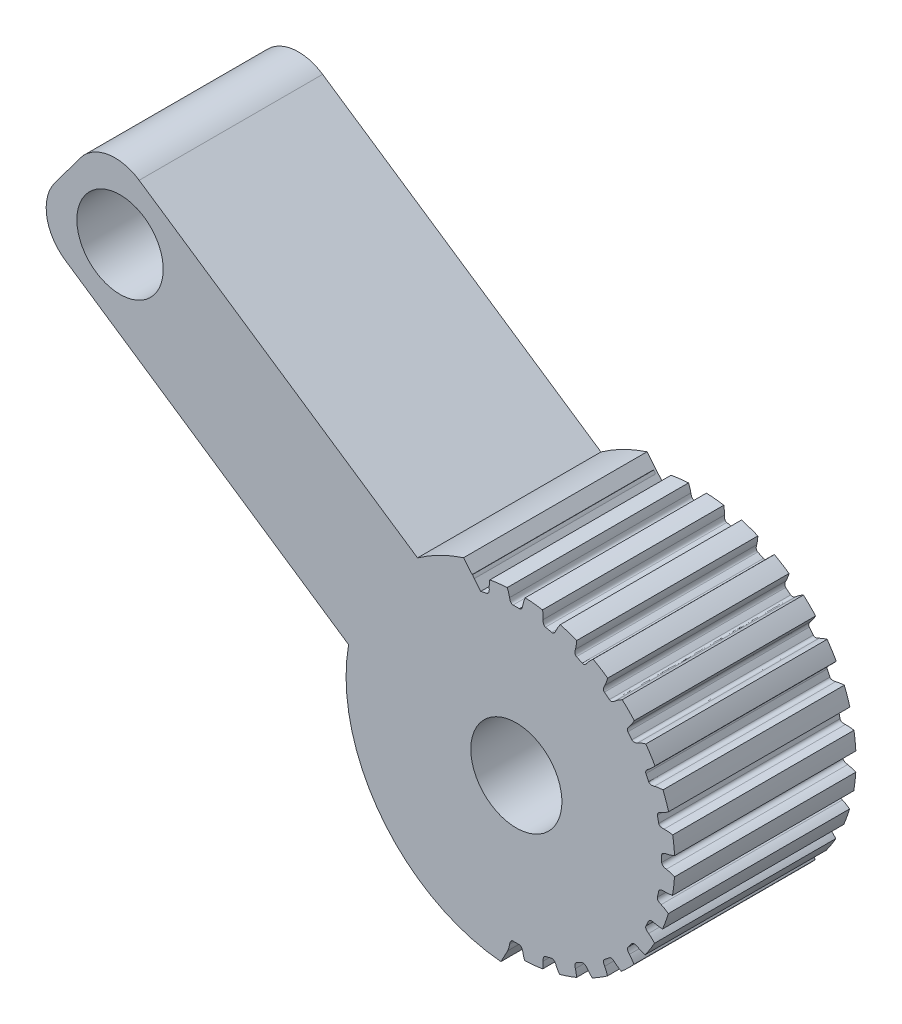
SolidWorks part; units mm, degrees
ref_plane "Front Plane" through (0, 0, 0) normal (0, 0, 1) x (1, 0, 0)
ref_plane "Top Plane" through (0, 0, 0) normal (0, 1, 0) x (1, 0, 0)
ref_plane "Right Plane" through (0, 0, 0) normal (1, 0, 0) x (0, 0, -1)
sketch "Sketch1" plane through (0, 0, 0) normal (0, 0, 1) x (1, 0, 0)
  circle A0 centre (0, 0) radius 51
  spline B0 degree 3 poles (-154.887, 66.78) (-155.2147, 66.8751) (-155.972, 67.0749) (-157.2665, 67.3592) (-158.8688, 67.6411) (-160.7804, 67.8949) (-163.0012, 68.0947) (-165.5296, 68.2148) (-168.3623, 68.2292) (-171.4943, 68.1124) (-174.9189, 67.8391) (-177.2922, 67.5479) (-178.5249, 67.3712) knots 0 0 0 0 0.040302 0.092469 0.156501 0.232397 0.320159 0.419784 0.531275 0.65463 0.789849 0.936934 0.936934 0.936934 0.936934
  spline B1 degree 3 poles (-32.9524, 160.1409) (-32.7131, 160.19) (-32.2573, 160.3561) (-31.6871, 160.7688) (-31.2499, 161.2756) (-30.925, 161.8346) (-30.6851, 162.433) (-30.5112, 163.0721) (-30.3923, 163.7568) (-30.3235, 164.4918) (-30.3029, 165.2808) (-30.3207, 165.8245) (-30.3369, 166.1054) knots 0 0 0 0 0.028845 0.056347 0.082281 0.107325 0.132381 0.15822 0.185411 0.214359 0.245345 0.278571 0.278571 0.278571 0.278571
  spline B2 degree 3 poles (-30.3369, 166.1054) (-30.3567, 166.446) (-30.383, 167.2288) (-30.3721, 168.5541) (-30.2904, 170.179) (-30.1125, 172.0991) (-29.8131, 174.3087) (-29.3675, 176.8004) (-28.7513, 179.5653) (-27.9405, 182.5927) (-26.9119, 185.8707) (-26.1, 188.1197) (-25.6534, 189.2821) knots 0 0 0 0 0.040302 0.092469 0.156501 0.232397 0.320159 0.419784 0.531275 0.65463 0.789849 0.936934 0.936934 0.936934 0.936934
  spline B3 degree 3 poles (-3.6912, 163.4378) (-3.9354, 163.4325) (-4.4167, 163.493) (-5.0645, 163.7685) (-5.6035, 164.1653) (-6.0446, 164.638) (-6.4117, 165.168) (-6.7235, 165.7523) (-6.9917, 166.3934) (-7.2223, 167.0947) (-7.418, 167.8593) (-7.5217, 168.3933) (-7.5683, 168.6708) knots 0 0 0 0 0.028845 0.056347 0.082281 0.107325 0.132381 0.15822 0.185411 0.214359 0.245345 0.278571 0.278571 0.278571 0.278571
  arc B4 (-163.6485, -97.2678) -> (-159.1718, -104.3926) centre (-0.1485, 0.4972) ccw
  spline B5 degree 3 poles (162.1575, 45.1531) (162.473, 45.2831) (163.1896, 45.599) (164.379, 46.1839) (165.8075, 46.9625) (167.4603, 47.9559) (169.3212, 49.1843) (171.3728, 50.6669) (173.5965, 52.4218) (175.9723, 54.4658) (178.4794, 56.8148) (180.1534, 58.5221) (181.0069, 59.4289) knots 0 0 0 0 0.040302 0.092469 0.156501 0.232397 0.320159 0.419784 0.531275 0.65463 0.789849 0.936934 0.936934 0.936934 0.936934
  spline B6 degree 3 poles (-162.4546, 45.1531) (-162.7701, 45.2831) (-163.4867, 45.599) (-164.6761, 46.1839) (-166.1046, 46.9625) (-167.7574, 47.9559) (-169.6183, 49.1843) (-171.6699, 50.6669) (-173.8935, 52.4218) (-176.2694, 54.4658) (-178.7765, 56.8148) (-180.4505, 58.5221) (-181.304, 59.4289) knots 0 0 0 0 0.040302 0.092469 0.156501 0.232397 0.320159 0.419784 0.531275 0.65463 0.789849 0.936934 0.936934 0.936934 0.936934
  spline B7 degree 3 poles (-168.3221, -6.9226) (-168.6586, -6.9791) (-169.4276, -7.1277) (-170.7173, -7.4332) (-172.2832, -7.8744) (-174.1156, -8.4751) (-176.2032, -9.2587) (-178.5333, -10.2476) (-181.0917, -11.4636) (-183.8629, -12.9277) (-186.8298, -14.6599) (-188.8417, -15.9519) (-189.8756, -16.646) knots 0 0 0 0 0.040302 0.092469 0.156501 0.232397 0.320159 0.419784 0.531275 0.65463 0.789849 0.936934 0.936934 0.936934 0.936934
  spline B8 degree 3 poles (-165.7567, -29.6912) (-166.0973, -29.7109) (-166.8801, -29.7372) (-168.2055, -29.7264) (-169.8303, -29.6447) (-171.7504, -29.4667) (-173.96, -29.1674) (-176.4517, -28.7218) (-179.2166, -28.1055) (-182.2441, -27.2947) (-185.5221, -26.2662) (-187.771, -25.4543) (-188.9335, -25.0076) knots 0 0 0 0 0.040302 0.092469 0.156501 0.232397 0.320159 0.419784 0.531275 0.65463 0.789849 0.936934 0.936934 0.936934 0.936934
  arc B9 (3.3942, 163.4378) -> (-3.6912, 163.4378) centre (-0.1485, 0.4972) ccw
  spline B10 degree 3 poles (-7.5683, 168.6708) (-7.6249, 169.0073) (-7.7734, 169.7762) (-8.0789, 171.066) (-8.5201, 172.6319) (-9.1209, 174.4643) (-9.9044, 176.5519) (-10.8933, 178.882) (-12.1093, 181.4404) (-13.5735, 184.2115) (-15.3057, 187.1784) (-16.5977, 189.1903) (-17.2918, 190.2243) knots 0 0 0 0 0.040302 0.092469 0.156501 0.232397 0.320159 0.419784 0.531275 0.65463 0.789849 0.936934 0.936934 0.936934 0.936934
  arc B11 (-17.2918, 190.2243) -> (-25.6534, 189.2821) centre (-0.1485, 0.4972) ccw
  arc B12 (-32.9524, 160.1409) -> (-39.8601, 158.5642) centre (-0.1485, 0.4972) ccw
  spline B13 degree 3 poles (-39.8601, 158.5642) (-40.097, 158.5047) (-40.5797, 158.4566) (-41.2725, 158.581) (-41.8863, 158.8479) (-42.4216, 159.2106) (-42.8973, 159.6457) (-43.3314, 160.1459) (-43.7355, 160.7113) (-44.1164, 161.3437) (-44.4773, 162.0456) (-44.6972, 162.5432) (-44.8044, 162.8033) knots 0 0 0 0 0.028845 0.056347 0.082281 0.107325 0.132381 0.15822 0.185411 0.214359 0.245345 0.278571 0.278571 0.278571 0.278571
  spline B14 degree 3 poles (-44.8044, 162.8033) (-44.9344, 163.1187) (-45.2504, 163.8354) (-45.8352, 165.0248) (-46.6138, 166.4533) (-47.6072, 168.106) (-48.8356, 169.9669) (-50.3182, 172.0185) (-52.0731, 174.2422) (-54.1172, 176.6181) (-56.4661, 179.1252) (-58.1734, 180.7991) (-59.0802, 181.6527) knots 0 0 0 0 0.040302 0.092469 0.156501 0.232397 0.320159 0.419784 0.531275 0.65463 0.789849 0.936934 0.936934 0.936934 0.936934
  arc B15 (-59.0802, 181.6527) -> (-67.0225, 178.8736) centre (-0.1485, 0.4972) ccw
  spline B16 degree 3 poles (-66.4313, 155.2357) (-66.5264, 155.5634) (-66.7262, 156.3207) (-67.0105, 157.6152) (-67.2925, 159.2175) (-67.5462, 161.1291) (-67.7461, 163.3499) (-67.8661, 165.8783) (-67.8805, 168.7109) (-67.7637, 171.8429) (-67.4904, 175.2676) (-67.1993, 177.6409) (-67.0225, 178.8736) knots 0 0 0 0 0.040302 0.092469 0.156501 0.232397 0.320159 0.419784 0.531275 0.65463 0.789849 0.936934 0.936934 0.936934 0.936934
  spline B17 degree 3 poles (-67.6539, 148.8387) (-67.4317, 148.9399) (-67.0243, 149.2033) (-66.5601, 149.7325) (-66.2467, 150.3239) (-66.0543, 150.9411) (-65.9536, 151.5779) (-65.9262, 152.2397) (-65.9627, 152.9336) (-66.0592, 153.6656) (-66.2147, 154.4394) (-66.353, 154.9655) (-66.4313, 155.2357) knots 0 0 0 0 0.028845 0.056347 0.082281 0.107325 0.132381 0.15822 0.185411 0.214359 0.245345 0.278571 0.278571 0.278571 0.278571
  arc B18 (-67.6539, 148.8387) -> (-74.0377, 145.7645) centre (-0.1485, 0.4972) ccw
  spline B19 degree 3 poles (-74.0377, 145.7645) (-74.2554, 145.6538) (-74.7153, 145.4995) (-75.4184, 145.4665) (-76.0762, 145.5902) (-76.6788, 145.8247) (-77.2394, 146.143) (-77.7739, 146.5341) (-78.2937, 146.9954) (-78.8058, 147.5272) (-79.3138, 148.1312) (-79.6389, 148.5673) (-79.8013, 148.797) knots 0 0 0 0 0.028845 0.056347 0.082281 0.107325 0.132381 0.15822 0.185411 0.214359 0.245345 0.278571 0.278571 0.278571 0.278571
  spline B20 degree 3 poles (-79.8013, 148.797) (-79.9983, 149.0757) (-80.4657, 149.704) (-81.3006, 150.7335) (-82.3775, 151.9529) (-83.7138, 153.3432) (-85.3255, 154.8841) (-87.2275, 156.5543) (-89.4331, 158.3318) (-91.9546, 160.1932) (-94.8026, 162.1147) (-96.8396, 163.3668) (-97.9135, 163.9972) knots 0 0 0 0 0.040302 0.092469 0.156501 0.232397 0.320159 0.419784 0.531275 0.65463 0.789849 0.936934 0.936934 0.936934 0.936934
  arc B21 (-97.9135, 163.9972) -> (-105.0383, 159.5204) centre (-0.1485, 0.4972) ccw
  spline B22 degree 3 poles (-99.202, 136.6067) (-99.3676, 136.9051) (-99.7309, 137.5989) (-100.2962, 138.7977) (-100.9276, 140.2971) (-101.6004, 142.1043) (-102.2894, 144.225) (-102.969, 146.6633) (-103.6134, 149.4217) (-104.1965, 152.5011) (-104.6921, 155.9008) (-104.9363, 158.2793) (-105.0383, 159.5204) knots 0 0 0 0 0.040302 0.092469 0.156501 0.232397 0.320159 0.419784 0.531275 0.65463 0.789849 0.936934 0.936934 0.936934 0.936934
  spline B23 degree 3 poles (-98.9705, 130.0981) (-98.7763, 130.2462) (-98.4378, 130.5936) (-98.103, 131.2129) (-97.929, 131.8592) (-97.8789, 132.5038) (-97.9224, 133.147) (-98.0429, 133.7983) (-98.2329, 134.4667) (-98.4899, 135.1588) (-98.8136, 135.8786) (-99.0655, 136.3608) (-99.202, 136.6067) knots 0 0 0 0 0.028845 0.056347 0.082281 0.107325 0.132381 0.15822 0.185411 0.214359 0.245345 0.278571 0.278571 0.278571 0.278571
  arc B24 (-98.9705, 130.0981) -> (-104.5101, 125.6805) centre (-0.1485, 0.4972) ccw
  spline B25 degree 3 poles (-104.5101, 125.6805) (-104.6977, 125.5241) (-105.1118, 125.2713) (-105.79, 125.0827) (-106.4588, 125.0569) (-107.0984, 125.1515) (-107.7158, 125.337) (-108.3239, 125.5994) (-108.9333, 125.9334) (-109.5509, 126.3379) (-110.1806, 126.8137) (-110.5946, 127.1666) (-110.804, 127.3544) knots 0 0 0 0 0.028845 0.056347 0.082281 0.107325 0.132381 0.15822 0.185411 0.214359 0.245345 0.278571 0.278571 0.278571 0.278571
  spline B26 degree 3 poles (-110.804, 127.3544) (-111.0581, 127.5823) (-111.6537, 128.0909) (-112.6966, 128.9087) (-114.0179, 129.8579) (-115.6301, 130.916) (-117.5443, 132.0596) (-119.7702, 133.2648) (-122.3161, 134.5068) (-125.1886, 135.7605) (-128.3927, 137.0001) (-130.6572, 137.7676) (-131.8446, 138.1432) knots 0 0 0 0 0.040302 0.092469 0.156501 0.232397 0.320159 0.419784 0.531275 0.65463 0.789849 0.936934 0.936934 0.936934 0.936934
  arc B27 (-131.8446, 138.1432) -> (-137.7945, 132.1932) centre (-0.1485, 0.4972) ccw
  spline B28 degree 3 poles (-127.0058, 111.1527) (-127.2336, 111.4067) (-127.7422, 112.0023) (-128.5601, 113.0453) (-129.5093, 114.3666) (-130.5673, 115.9787) (-131.7109, 117.8929) (-132.9161, 120.1189) (-134.1582, 122.6647) (-135.4119, 125.5372) (-136.6515, 128.7414) (-137.4189, 131.0059) (-137.7945, 132.1932) knots 0 0 0 0 0.040302 0.092469 0.156501 0.232397 0.320159 0.419784 0.531275 0.65463 0.789849 0.936934 0.936934 0.936934 0.936934
  spline B29 degree 3 poles (-125.3318, 104.8588) (-125.1754, 105.0464) (-124.9226, 105.4604) (-124.7341, 106.1386) (-124.7082, 106.8074) (-124.8028, 107.4471) (-124.9883, 108.0645) (-125.2508, 108.6726) (-125.5847, 109.282) (-125.9893, 109.8996) (-126.4651, 110.5293) (-126.8179, 110.9433) (-127.0058, 111.1527) knots 0 0 0 0 0.028845 0.056347 0.082281 0.107325 0.132381 0.15822 0.185411 0.214359 0.245345 0.278571 0.278571 0.278571 0.278571
  arc B30 (-125.3318, 104.8588) -> (-129.7495, 99.3192) centre (-0.1485, 0.4972) ccw
  spline B31 degree 3 poles (-129.7495, 99.3192) (-129.8975, 99.125) (-130.245, 98.7864) (-130.8642, 98.4517) (-131.5105, 98.2777) (-132.1551, 98.2275) (-132.7983, 98.271) (-133.4496, 98.3916) (-134.118, 98.5816) (-134.8102, 98.8385) (-135.5299, 99.1623) (-136.0121, 99.4142) (-136.2581, 99.5507) knots 0 0 0 0 0.028845 0.056347 0.082281 0.107325 0.132381 0.15822 0.185411 0.214359 0.245345 0.278571 0.278571 0.278571 0.278571
  spline B32 degree 3 poles (-136.2581, 99.5507) (-136.5564, 99.7163) (-137.2502, 100.0796) (-138.4491, 100.6449) (-139.9484, 101.2763) (-141.7556, 101.9491) (-143.8763, 102.6381) (-146.3146, 103.3177) (-149.073, 103.9621) (-152.1525, 104.5452) (-155.5521, 105.0407) (-157.9306, 105.285) (-159.1718, 105.387) knots 0 0 0 0 0.040302 0.092469 0.156501 0.232397 0.320159 0.419784 0.531275 0.65463 0.789849 0.936934 0.936934 0.936934 0.936934
  arc B33 (-159.1718, 105.387) -> (-163.6485, 98.2622) centre (-0.1485, 0.4972) ccw
  spline B34 degree 3 poles (-148.4484, 80.15) (-148.727, 80.3469) (-149.3554, 80.8144) (-150.3848, 81.6492) (-151.6042, 82.7262) (-152.9945, 84.0625) (-154.5354, 85.6742) (-156.2057, 87.5761) (-157.9831, 89.7818) (-159.8446, 92.3033) (-161.7661, 95.1513) (-163.0182, 97.1882) (-163.6485, 98.2622) knots 0 0 0 0 0.040302 0.092469 0.156501 0.232397 0.320159 0.419784 0.531275 0.65463 0.789849 0.936934 0.936934 0.936934 0.936934
  spline B35 degree 3 poles (-145.4158, 74.3863) (-145.3051, 74.604) (-145.1508, 75.064) (-145.1179, 75.7671) (-145.2415, 76.4249) (-145.476, 77.0274) (-145.7943, 77.5881) (-146.1855, 78.1225) (-146.6467, 78.6423) (-147.1785, 79.1544) (-147.7825, 79.6625) (-148.2186, 79.9876) (-148.4484, 80.15) knots 0 0 0 0 0.028845 0.056347 0.082281 0.107325 0.132381 0.15822 0.185411 0.214359 0.245345 0.278571 0.278571 0.278571 0.278571
  arc B36 (-145.4158, 74.3863) -> (-148.4901, 68.0026) centre (-0.1485, 0.4972) ccw
  spline B37 degree 3 poles (-148.4901, 68.0026) (-148.5912, 67.7803) (-148.8546, 67.3729) (-149.3838, 66.9088) (-149.9752, 66.5953) (-150.5925, 66.403) (-151.2293, 66.3023) (-151.891, 66.2749) (-152.585, 66.3114) (-153.3169, 66.4079) (-154.0907, 66.5633) (-154.6168, 66.7016) (-154.887, 66.78) knots 0 0 0 0 0.028845 0.056347 0.082281 0.107325 0.132381 0.15822 0.185411 0.214359 0.245345 0.278571 0.278571 0.278571 0.278571
  arc B38 (-178.5249, 67.3712) -> (-181.304, 59.4289) centre (-0.1485, 0.4972) ccw
  spline B39 degree 3 poles (-158.2155, 40.2088) (-158.156, 40.4456) (-158.108, 40.9284) (-158.2323, 41.6212) (-158.4992, 42.235) (-158.8619, 42.7702) (-159.297, 43.246) (-159.7973, 43.68) (-160.3626, 44.0842) (-160.995, 44.4651) (-161.6969, 44.826) (-162.1945, 45.0459) (-162.4546, 45.1531) knots 0 0 0 0 0.028845 0.056347 0.082281 0.107325 0.132381 0.15822 0.185411 0.214359 0.245345 0.278571 0.278571 0.278571 0.278571
  arc B40 (-158.2155, 40.2088) -> (-159.7922, 33.301) centre (-0.1485, 0.4972) ccw
  spline B41 degree 3 poles (-159.7922, 33.301) (-159.8414, 33.0618) (-160.0075, 32.606) (-160.4201, 32.0357) (-160.9269, 31.5986) (-161.4859, 31.2737) (-162.0844, 31.0338) (-162.7234, 30.8598) (-163.4081, 30.741) (-164.1432, 30.6722) (-164.9321, 30.6516) (-165.4758, 30.6693) (-165.7567, 30.6856) knots 0 0 0 0 0.028845 0.056347 0.082281 0.107325 0.132381 0.15822 0.185411 0.214359 0.245345 0.278571 0.278571 0.278571 0.278571
  spline B42 degree 3 poles (-165.7567, 30.6856) (-166.0973, 30.7054) (-166.8801, 30.7316) (-168.2055, 30.7208) (-169.8303, 30.6391) (-171.7504, 30.4612) (-173.96, 30.1618) (-176.4517, 29.7162) (-179.2166, 29.0999) (-182.2441, 28.2891) (-185.5221, 27.2606) (-187.771, 26.4487) (-188.9335, 26.002) knots 0 0 0 0 0.040302 0.092469 0.156501 0.232397 0.320159 0.419784 0.531275 0.65463 0.789849 0.936934 0.936934 0.936934 0.936934
  arc B43 (-188.9335, 26.002) -> (-189.8756, 17.6404) centre (-0.1485, 0.4972) ccw
  spline B44 degree 3 poles (-168.3221, 7.917) (-168.6586, 7.9735) (-169.4276, 8.1221) (-170.7173, 8.4276) (-172.2832, 8.8688) (-174.1156, 9.4695) (-176.2032, 10.2531) (-178.5333, 11.242) (-181.0917, 12.458) (-183.8629, 13.9221) (-186.8298, 15.6543) (-188.8417, 16.9463) (-189.8756, 17.6404) knots 0 0 0 0 0.040302 0.092469 0.156501 0.232397 0.320159 0.419784 0.531275 0.65463 0.789849 0.936934 0.936934 0.936934 0.936934
  spline B45 degree 3 poles (-163.0891, 4.0399) (-163.0838, 4.2841) (-163.1444, 4.7654) (-163.4198, 5.4132) (-163.8166, 5.9522) (-164.2893, 6.3933) (-164.8193, 6.7603) (-165.4036, 7.0722) (-166.0447, 7.3404) (-166.7461, 7.571) (-167.5107, 7.7667) (-168.0447, 7.8703) (-168.3221, 7.917) knots 0 0 0 0 0.028845 0.056347 0.082281 0.107325 0.132381 0.15822 0.185411 0.214359 0.245345 0.278571 0.278571 0.278571 0.278571
  arc B46 (-163.0891, 4.0399) -> (-163.0891, -3.0455) centre (-0.1485, 0.4972) ccw
  spline B47 degree 3 poles (-163.0891, -3.0455) (-163.0838, -3.2897) (-163.1444, -3.771) (-163.4198, -4.4188) (-163.8166, -4.9578) (-164.2893, -5.3989) (-164.8193, -5.7659) (-165.4036, -6.0777) (-166.0447, -6.3459) (-166.7461, -6.5766) (-167.5107, -6.7723) (-168.0447, -6.8759) (-168.3221, -6.9226) knots 0 0 0 0 0.028845 0.056347 0.082281 0.107325 0.132381 0.15822 0.185411 0.214359 0.245345 0.278571 0.278571 0.278571 0.278571
  arc B48 (-189.8756, -16.646) -> (-188.9335, -25.0076) centre (-0.1485, 0.4972) ccw
  spline B49 degree 3 poles (-159.7922, -32.3066) (-159.8414, -32.0674) (-160.0075, -31.6116) (-160.4201, -31.0413) (-160.9269, -30.6041) (-161.4859, -30.2793) (-162.0844, -30.0394) (-162.7234, -29.8654) (-163.4081, -29.7466) (-164.1432, -29.6778) (-164.9321, -29.6572) (-165.4758, -29.6749) (-165.7567, -29.6912) knots 0 0 0 0 0.028845 0.056347 0.082281 0.107325 0.132381 0.15822 0.185411 0.214359 0.245345 0.278571 0.278571 0.278571 0.278571
  arc B50 (-159.7922, -32.3066) -> (-158.2155, -39.2144) centre (-0.1485, 0.4972) ccw
  spline B51 degree 3 poles (-158.2155, -39.2144) (-158.156, -39.4512) (-158.108, -39.934) (-158.2323, -40.6268) (-158.4992, -41.2406) (-158.8619, -41.7758) (-159.297, -42.2516) (-159.7973, -42.6856) (-160.3626, -43.0897) (-160.995, -43.4707) (-161.6969, -43.8316) (-162.1945, -44.0515) (-162.4546, -44.1587) knots 0 0 0 0 0.028845 0.056347 0.082281 0.107325 0.132381 0.15822 0.185411 0.214359 0.245345 0.278571 0.278571 0.278571 0.278571
  spline B52 degree 3 poles (-162.4546, -44.1587) (-162.7701, -44.2887) (-163.4867, -44.6046) (-164.6761, -45.1894) (-166.1046, -45.968) (-167.7574, -46.9615) (-169.6183, -48.1899) (-171.6699, -49.6725) (-173.8935, -51.4274) (-176.2694, -53.4714) (-178.7765, -55.8204) (-180.4505, -57.5277) (-181.304, -58.4345) knots 0 0 0 0 0.040302 0.092469 0.156501 0.232397 0.320159 0.419784 0.531275 0.65463 0.789849 0.936934 0.936934 0.936934 0.936934
  arc B53 (-181.304, -58.4345) -> (-178.5249, -66.3768) centre (-0.1485, 0.4972) ccw
  spline B54 degree 3 poles (-154.887, -65.7856) (-155.2147, -65.8806) (-155.972, -66.0804) (-157.2665, -66.3648) (-158.8688, -66.6467) (-160.7804, -66.9005) (-163.0012, -67.1003) (-165.5296, -67.2203) (-168.3623, -67.2348) (-171.4943, -67.118) (-174.9189, -66.8446) (-177.2922, -66.5535) (-178.5249, -66.3768) knots 0 0 0 0 0.040302 0.092469 0.156501 0.232397 0.320159 0.419784 0.531275 0.65463 0.789849 0.936934 0.936934 0.936934 0.936934
  spline B55 degree 3 poles (-148.4901, -67.0082) (-148.5912, -66.7859) (-148.8546, -66.3785) (-149.3838, -65.9144) (-149.9752, -65.6009) (-150.5925, -65.4086) (-151.2293, -65.3079) (-151.891, -65.2805) (-152.585, -65.317) (-153.3169, -65.4135) (-154.0907, -65.5689) (-154.6168, -65.7072) (-154.887, -65.7856) knots 0 0 0 0 0.028845 0.056347 0.082281 0.107325 0.132381 0.15822 0.185411 0.214359 0.245345 0.278571 0.278571 0.278571 0.278571
  arc B56 (-148.4901, -67.0082) -> (-145.4158, -73.3919) centre (-0.1485, 0.4972) ccw
  spline B57 degree 3 poles (-145.4158, -73.3919) (-145.3051, -73.6096) (-145.1508, -74.0695) (-145.1179, -74.7727) (-145.2415, -75.4305) (-145.476, -76.033) (-145.7943, -76.5937) (-146.1855, -77.1281) (-146.6467, -77.6479) (-147.1785, -78.16) (-147.7825, -78.6681) (-148.2186, -78.9932) (-148.4484, -79.1555) knots 0 0 0 0 0.028845 0.056347 0.082281 0.107325 0.132381 0.15822 0.185411 0.214359 0.245345 0.278571 0.278571 0.278571 0.278571
  spline B58 degree 3 poles (-148.4484, -79.1555) (-148.727, -79.3525) (-149.3554, -79.82) (-150.3848, -80.6548) (-151.6042, -81.7318) (-152.9945, -83.0681) (-154.5354, -84.6798) (-156.2057, -86.5817) (-157.9831, -88.7874) (-159.8446, -91.3089) (-161.7661, -94.1568) (-163.0182, -96.1938) (-163.6485, -97.2678) knots 0 0 0 0 0.040302 0.092469 0.156501 0.232397 0.320159 0.419784 0.531275 0.65463 0.789849 0.936934 0.936934 0.936934 0.936934
  spline B59 degree 3 poles (-136.2581, -98.5563) (-136.5564, -98.7219) (-137.2502, -99.0852) (-138.4491, -99.6505) (-139.9484, -100.2819) (-141.7556, -100.9546) (-143.8763, -101.6436) (-146.3146, -102.3233) (-149.073, -102.9677) (-152.1525, -103.5508) (-155.5521, -104.0463) (-157.9306, -104.2906) (-159.1718, -104.3926) knots 0 0 0 0 0.040302 0.092469 0.156501 0.232397 0.320159 0.419784 0.531275 0.65463 0.789849 0.936934 0.936934 0.936934 0.936934
  spline B60 degree 3 poles (-129.7495, -98.3248) (-129.8975, -98.1306) (-130.245, -97.792) (-130.8642, -97.4573) (-131.5105, -97.2833) (-132.1551, -97.2331) (-132.7983, -97.2766) (-133.4496, -97.3972) (-134.118, -97.5872) (-134.8102, -97.8441) (-135.5299, -98.1679) (-136.0121, -98.4198) (-136.2581, -98.5563) knots 0 0 0 0 0.028845 0.056347 0.082281 0.107325 0.132381 0.15822 0.185411 0.214359 0.245345 0.278571 0.278571 0.278571 0.278571
  arc B61 (-129.7495, -98.3248) -> (-125.3318, -103.8644) centre (-0.1485, 0.4972) ccw
  spline B62 degree 3 poles (-125.3318, -103.8644) (-125.1754, -104.052) (-124.9226, -104.466) (-124.7341, -105.1442) (-124.7082, -105.813) (-124.8028, -106.4526) (-124.9883, -107.0701) (-125.2508, -107.6782) (-125.5847, -108.2876) (-125.9893, -108.9052) (-126.4651, -109.5349) (-126.8179, -109.9489) (-127.0058, -110.1583) knots 0 0 0 0 0.028845 0.056347 0.082281 0.107325 0.132381 0.15822 0.185411 0.214359 0.245345 0.278571 0.278571 0.278571 0.278571
  spline B63 degree 3 poles (-127.0058, -110.1583) (-127.2336, -110.4123) (-127.7422, -111.0079) (-128.5601, -112.0509) (-129.5093, -113.3722) (-130.5673, -114.9843) (-131.7109, -116.8985) (-132.9161, -119.1245) (-134.1582, -121.6703) (-135.4119, -124.5428) (-136.6515, -127.747) (-137.4189, -130.0115) (-137.7945, -131.1988) knots 0 0 0 0 0.040302 0.092469 0.156501 0.232397 0.320159 0.419784 0.531275 0.65463 0.789849 0.936934 0.936934 0.936934 0.936934
  arc B64 (-137.7945, -131.1988) -> (-131.8446, -137.1488) centre (-0.1485, 0.4972) ccw
  spline B65 degree 3 poles (-110.804, -126.36) (-111.0581, -126.5879) (-111.6537, -127.0964) (-112.6966, -127.9143) (-114.0179, -128.8635) (-115.6301, -129.9216) (-117.5443, -131.0652) (-119.7702, -132.2704) (-122.3161, -133.5124) (-125.1886, -134.7661) (-128.3927, -136.0057) (-130.6572, -136.7732) (-131.8446, -137.1488) knots 0 0 0 0 0.040302 0.092469 0.156501 0.232397 0.320159 0.419784 0.531275 0.65463 0.789849 0.936934 0.936934 0.936934 0.936934
  spline B66 degree 3 poles (-104.5101, -124.686) (-104.6977, -124.5297) (-105.1118, -124.2769) (-105.79, -124.0883) (-106.4588, -124.0625) (-107.0984, -124.157) (-107.7158, -124.3426) (-108.3239, -124.605) (-108.9333, -124.939) (-109.5509, -125.3435) (-110.1806, -125.8193) (-110.5946, -126.1722) (-110.804, -126.36) knots 0 0 0 0 0.028845 0.056347 0.082281 0.107325 0.132381 0.15822 0.185411 0.214359 0.245345 0.278571 0.278571 0.278571 0.278571
  arc B67 (-104.5101, -124.686) -> (-98.9705, -129.1037) centre (-0.1485, 0.4972) ccw
  spline B68 degree 3 poles (-98.9705, -129.1037) (-98.7763, -129.2518) (-98.4378, -129.5992) (-98.103, -130.2185) (-97.929, -130.8648) (-97.8789, -131.5094) (-97.9224, -132.1526) (-98.0429, -132.8038) (-98.2329, -133.4723) (-98.4899, -134.1644) (-98.8136, -134.8842) (-99.0655, -135.3664) (-99.202, -135.6123) knots 0 0 0 0 0.028845 0.056347 0.082281 0.107325 0.132381 0.15822 0.185411 0.214359 0.245345 0.278571 0.278571 0.278571 0.278571
  spline B69 degree 3 poles (-99.202, -135.6123) (-99.3676, -135.9107) (-99.7309, -136.6045) (-100.2962, -137.8033) (-100.9276, -139.3027) (-101.6004, -141.1099) (-102.2894, -143.2305) (-102.969, -145.6689) (-103.6134, -148.4273) (-104.1965, -151.5067) (-104.6921, -154.9064) (-104.9363, -157.2849) (-105.0383, -158.526) knots 0 0 0 0 0.040302 0.092469 0.156501 0.232397 0.320159 0.419784 0.531275 0.65463 0.789849 0.936934 0.936934 0.936934 0.936934
  arc B70 (-105.0383, -158.526) -> (-97.9135, -163.0028) centre (-0.1485, 0.4972) ccw
  spline B71 degree 3 poles (-79.8013, -147.8026) (-79.9983, -148.0813) (-80.4657, -148.7096) (-81.3006, -149.7391) (-82.3775, -150.9585) (-83.7138, -152.3488) (-85.3255, -153.8896) (-87.2275, -155.5599) (-89.4331, -157.3373) (-91.9546, -159.1988) (-94.8026, -161.1203) (-96.8396, -162.3724) (-97.9135, -163.0028) knots 0 0 0 0 0.040302 0.092469 0.156501 0.232397 0.320159 0.419784 0.531275 0.65463 0.789849 0.936934 0.936934 0.936934 0.936934
  spline B72 degree 3 poles (-74.0377, -144.7701) (-74.2554, -144.6594) (-74.7153, -144.5051) (-75.4184, -144.4721) (-76.0762, -144.5958) (-76.6788, -144.8303) (-77.2394, -145.1486) (-77.7739, -145.5397) (-78.2937, -146.0009) (-78.8058, -146.5328) (-79.3138, -147.1368) (-79.6389, -147.5729) (-79.8013, -147.8026) knots 0 0 0 0 0.028845 0.056347 0.082281 0.107325 0.132381 0.15822 0.185411 0.214359 0.245345 0.278571 0.278571 0.278571 0.278571
  arc B73 (-74.0377, -144.7701) -> (-67.6539, -147.8443) centre (-0.1485, 0.4972) ccw
  spline B74 degree 3 poles (-67.6539, -147.8443) (-67.4317, -147.9455) (-67.0243, -148.2089) (-66.5601, -148.7381) (-66.2467, -149.3294) (-66.0543, -149.9467) (-65.9536, -150.5835) (-65.9262, -151.2453) (-65.9627, -151.9392) (-66.0592, -152.6712) (-66.2147, -153.445) (-66.353, -153.9711) (-66.4313, -154.2413) knots 0 0 0 0 0.028845 0.056347 0.082281 0.107325 0.132381 0.15822 0.185411 0.214359 0.245345 0.278571 0.278571 0.278571 0.278571
  spline B75 degree 3 poles (-66.4313, -154.2413) (-66.5264, -154.569) (-66.7262, -155.3262) (-67.0105, -156.6208) (-67.2925, -158.2231) (-67.5462, -160.1346) (-67.7461, -162.3555) (-67.8661, -164.8839) (-67.8805, -167.7165) (-67.7637, -170.8485) (-67.4904, -174.2732) (-67.1993, -176.6464) (-67.0225, -177.8791) knots 0 0 0 0 0.040302 0.092469 0.156501 0.232397 0.320159 0.419784 0.531275 0.65463 0.789849 0.936934 0.936934 0.936934 0.936934
  arc B76 (-67.0225, -177.8791) -> (-59.0802, -180.6583) centre (-0.1485, 0.4972) ccw
  spline B77 degree 3 poles (-44.8044, -161.8088) (-44.9344, -162.1243) (-45.2504, -162.841) (-45.8352, -164.0304) (-46.6138, -165.4589) (-47.6072, -167.1116) (-48.8356, -168.9725) (-50.3182, -171.0241) (-52.0731, -173.2478) (-54.1172, -175.6237) (-56.4661, -178.1308) (-58.1734, -179.8047) (-59.0802, -180.6583) knots 0 0 0 0 0.040302 0.092469 0.156501 0.232397 0.320159 0.419784 0.531275 0.65463 0.789849 0.936934 0.936934 0.936934 0.936934
  spline B78 degree 3 poles (-39.8601, -157.5698) (-40.097, -157.5103) (-40.5797, -157.4622) (-41.2725, -157.5866) (-41.8863, -157.8535) (-42.4216, -158.2162) (-42.8973, -158.6513) (-43.3314, -159.1515) (-43.7355, -159.7169) (-44.1164, -160.3493) (-44.4773, -161.0512) (-44.6972, -161.5487) (-44.8044, -161.8088) knots 0 0 0 0 0.028845 0.056347 0.082281 0.107325 0.132381 0.15822 0.185411 0.214359 0.245345 0.278571 0.278571 0.278571 0.278571
  arc B79 (-39.8601, -157.5698) -> (-32.9524, -159.1464) centre (-0.1485, 0.4972) ccw
  spline B80 degree 3 poles (-32.9524, -159.1464) (-32.7131, -159.1956) (-32.2573, -159.3617) (-31.6871, -159.7744) (-31.2499, -160.2812) (-30.925, -160.8402) (-30.6851, -161.4386) (-30.5112, -162.0777) (-30.3923, -162.7623) (-30.3235, -163.4974) (-30.3029, -164.2864) (-30.3207, -164.8301) (-30.3369, -165.1109) knots 0 0 0 0 0.028845 0.056347 0.082281 0.107325 0.132381 0.15822 0.185411 0.214359 0.245345 0.278571 0.278571 0.278571 0.278571
  spline B81 degree 3 poles (-30.3369, -165.1109) (-30.3567, -165.4516) (-30.383, -166.2343) (-30.3721, -167.5597) (-30.2904, -169.1846) (-30.1125, -171.1047) (-29.8131, -173.3143) (-29.3675, -175.806) (-28.7513, -178.5709) (-27.9405, -181.5983) (-26.9119, -184.8763) (-26.1, -187.1253) (-25.6534, -188.2877) knots 0 0 0 0 0.040302 0.092469 0.156501 0.232397 0.320159 0.419784 0.531275 0.65463 0.789849 0.936934 0.936934 0.936934 0.936934
  arc B82 (-25.6534, -188.2877) -> (-17.2918, -189.2299) centre (-0.1485, 0.4972) ccw
  spline B83 degree 3 poles (-7.5683, -167.6764) (-7.6249, -168.0129) (-7.7734, -168.7818) (-8.0789, -170.0715) (-8.5201, -171.6375) (-9.1209, -173.4699) (-9.9044, -175.5574) (-10.8933, -177.8875) (-12.1093, -180.4459) (-13.5735, -183.2171) (-15.3057, -186.184) (-16.5977, -188.1959) (-17.2918, -189.2299) knots 0 0 0 0 0.040302 0.092469 0.156501 0.232397 0.320159 0.419784 0.531275 0.65463 0.789849 0.936934 0.936934 0.936934 0.936934
  spline B84 degree 3 poles (-3.6912, -162.4434) (-3.9354, -162.4381) (-4.4167, -162.4986) (-5.0645, -162.774) (-5.6035, -163.1708) (-6.0446, -163.6435) (-6.4117, -164.1736) (-6.7235, -164.7579) (-6.9917, -165.399) (-7.2223, -166.1003) (-7.418, -166.8649) (-7.5217, -167.3989) (-7.5683, -167.6764) knots 0 0 0 0 0.028845 0.056347 0.082281 0.107325 0.132381 0.15822 0.185411 0.214359 0.245345 0.278571 0.278571 0.278571 0.278571
  arc B85 (-3.6912, -162.4434) -> (3.3942, -162.4434) centre (-0.1485, 0.4972) ccw
  spline B86 degree 3 poles (3.3942, -162.4434) (3.6383, -162.4381) (4.1197, -162.4986) (4.7674, -162.774) (5.3064, -163.1708) (5.7476, -163.6435) (6.1146, -164.1736) (6.4264, -164.7579) (6.6946, -165.399) (6.9253, -166.1003) (7.1209, -166.8649) (7.2246, -167.3989) (7.2712, -167.6764) knots 0 0 0 0 0.028845 0.056347 0.082281 0.107325 0.132381 0.15822 0.185411 0.214359 0.245345 0.278571 0.278571 0.278571 0.278571
  spline B87 degree 3 poles (7.2712, -167.6764) (7.3278, -168.0129) (7.4763, -168.7818) (7.7818, -170.0715) (8.223, -171.6375) (8.8238, -173.4699) (9.6073, -175.5574) (10.5962, -177.8875) (11.8123, -180.4459) (13.2764, -183.2171) (15.0086, -186.184) (16.3006, -188.1959) (16.9947, -189.2299) knots 0 0 0 0 0.040302 0.092469 0.156501 0.232397 0.320159 0.419784 0.531275 0.65463 0.789849 0.936934 0.936934 0.936934 0.936934
  arc B88 (16.9947, -189.2299) -> (25.3563, -188.2877) centre (-0.1485, 0.4972) ccw
  spline B89 degree 3 poles (30.0399, -165.1109) (30.0596, -165.4516) (30.0859, -166.2343) (30.075, -167.5597) (29.9933, -169.1846) (29.8154, -171.1047) (29.516, -173.3143) (29.0704, -175.806) (28.4542, -178.5709) (27.6434, -181.5983) (26.6148, -184.8763) (25.8029, -187.1253) (25.3563, -188.2877) knots 0 0 0 0 0.040302 0.092469 0.156501 0.232397 0.320159 0.419784 0.531275 0.65463 0.789849 0.936934 0.936934 0.936934 0.936934
  spline B90 degree 3 poles (32.6553, -159.1464) (32.4161, -159.1956) (31.9603, -159.3617) (31.39, -159.7744) (30.9528, -160.2812) (30.6279, -160.8402) (30.3881, -161.4386) (30.2141, -162.0777) (30.0953, -162.7623) (30.0265, -163.4974) (30.0058, -164.2864) (30.0236, -164.8301) (30.0399, -165.1109) knots 0 0 0 0 0.028845 0.056347 0.082281 0.107325 0.132381 0.15822 0.185411 0.214359 0.245345 0.278571 0.278571 0.278571 0.278571
  arc B91 (32.6553, -159.1464) -> (39.563, -157.5698) centre (-0.1485, 0.4972) ccw
  spline B92 degree 3 poles (39.563, -157.5698) (39.7999, -157.5103) (40.2826, -157.4622) (40.9755, -157.5866) (41.5892, -157.8535) (42.1245, -158.2162) (42.6003, -158.6513) (43.0343, -159.1515) (43.4384, -159.7169) (43.8193, -160.3493) (44.1802, -161.0512) (44.4001, -161.5487) (44.5073, -161.8088) knots 0 0 0 0 0.028845 0.056347 0.082281 0.107325 0.132381 0.15822 0.185411 0.214359 0.245345 0.278571 0.278571 0.278571 0.278571
  spline B93 degree 3 poles (44.5073, -161.8088) (44.6374, -162.1243) (44.9533, -162.841) (45.5381, -164.0304) (46.3167, -165.4589) (47.3101, -167.1116) (48.5386, -168.9725) (50.0212, -171.0241) (51.776, -173.2478) (53.8201, -175.6237) (56.1691, -178.1308) (57.8763, -179.8047) (58.7831, -180.6583) knots 0 0 0 0 0.040302 0.092469 0.156501 0.232397 0.320159 0.419784 0.531275 0.65463 0.789849 0.936934 0.936934 0.936934 0.936934
  arc B94 (58.7831, -180.6583) -> (66.7254, -177.8791) centre (-0.1485, 0.4972) ccw
  spline B95 degree 3 poles (66.1343, -154.2413) (66.2293, -154.569) (66.4291, -155.3262) (66.7135, -156.6208) (66.9954, -158.2231) (67.2492, -160.1346) (67.449, -162.3555) (67.569, -164.8839) (67.5834, -167.7165) (67.4667, -170.8485) (67.1933, -174.2732) (66.9022, -176.6464) (66.7254, -177.8791) knots 0 0 0 0 0.040302 0.092469 0.156501 0.232397 0.320159 0.419784 0.531275 0.65463 0.789849 0.936934 0.936934 0.936934 0.936934
  spline B96 degree 3 poles (67.3569, -147.8443) (67.1346, -147.9455) (66.7272, -148.2089) (66.263, -148.7381) (65.9496, -149.3294) (65.7573, -149.9467) (65.6565, -150.5835) (65.6291, -151.2453) (65.6656, -151.9392) (65.7621, -152.6712) (65.9176, -153.445) (66.0559, -153.9711) (66.1343, -154.2413) knots 0 0 0 0 0.028845 0.056347 0.082281 0.107325 0.132381 0.15822 0.185411 0.214359 0.245345 0.278571 0.278571 0.278571 0.278571
  arc B97 (67.3569, -147.8443) -> (73.7406, -144.7701) centre (-0.1485, 0.4972) ccw
  spline B98 degree 3 poles (73.7406, -144.7701) (73.9583, -144.6594) (74.4182, -144.5051) (75.1213, -144.4721) (75.7791, -144.5958) (76.3817, -144.8303) (76.9423, -145.1486) (77.4768, -145.5397) (77.9966, -146.0009) (78.5087, -146.5328) (79.0167, -147.1368) (79.3418, -147.5729) (79.5042, -147.8026) knots 0 0 0 0 0.028845 0.056347 0.082281 0.107325 0.132381 0.15822 0.185411 0.214359 0.245345 0.278571 0.278571 0.278571 0.278571
  spline B99 degree 3 poles (79.5042, -147.8026) (79.7012, -148.0813) (80.1686, -148.7096) (81.0035, -149.7391) (82.0804, -150.9585) (83.4167, -152.3488) (85.0284, -153.8896) (86.9304, -155.5599) (89.1361, -157.3373) (91.6576, -159.1988) (94.5055, -161.1203) (96.5425, -162.3724) (97.6165, -163.0028) knots 0 0 0 0 0.040302 0.092469 0.156501 0.232397 0.320159 0.419784 0.531275 0.65463 0.789849 0.936934 0.936934 0.936934 0.936934
  arc B100 (97.6165, -163.0028) -> (104.7412, -158.526) centre (-0.1485, 0.4972) ccw
  spline B101 degree 3 poles (98.905, -135.6123) (99.0705, -135.9107) (99.4338, -136.6045) (99.9991, -137.8033) (100.6305, -139.3027) (101.3033, -141.1099) (101.9923, -143.2305) (102.6719, -145.6689) (103.3163, -148.4273) (103.8994, -151.5067) (104.395, -154.9064) (104.6393, -157.2849) (104.7412, -158.526) knots 0 0 0 0 0.040302 0.092469 0.156501 0.232397 0.320159 0.419784 0.531275 0.65463 0.789849 0.936934 0.936934 0.936934 0.936934
  spline B102 degree 3 poles (98.6735, -129.1037) (98.4793, -129.2518) (98.1407, -129.5992) (97.8059, -130.2185) (97.6319, -130.8648) (97.5818, -131.5094) (97.6253, -132.1526) (97.7458, -132.8038) (97.9358, -133.4723) (98.1928, -134.1644) (98.5165, -134.8842) (98.7684, -135.3664) (98.905, -135.6123) knots 0 0 0 0 0.028845 0.056347 0.082281 0.107325 0.132381 0.15822 0.185411 0.214359 0.245345 0.278571 0.278571 0.278571 0.278571
  arc B103 (98.6735, -129.1037) -> (104.2131, -124.686) centre (-0.1485, 0.4972) ccw
  spline B104 degree 3 poles (104.2131, -124.686) (104.4006, -124.5297) (104.8147, -124.2769) (105.4929, -124.0883) (106.1617, -124.0625) (106.8013, -124.157) (107.4187, -124.3426) (108.0268, -124.605) (108.6362, -124.939) (109.2538, -125.3435) (109.8835, -125.8193) (110.2975, -126.1722) (110.507, -126.36) knots 0 0 0 0 0.028845 0.056347 0.082281 0.107325 0.132381 0.15822 0.185411 0.214359 0.245345 0.278571 0.278571 0.278571 0.278571
  spline B105 degree 3 poles (110.507, -126.36) (110.761, -126.5879) (111.3566, -127.0964) (112.3995, -127.9143) (113.7208, -128.8635) (115.333, -129.9216) (117.2472, -131.0652) (119.4731, -132.2704) (122.019, -133.5124) (124.8915, -134.7661) (128.0956, -136.0057) (130.3601, -136.7732) (131.5475, -137.1488) knots 0 0 0 0 0.040302 0.092469 0.156501 0.232397 0.320159 0.419784 0.531275 0.65463 0.789849 0.936934 0.936934 0.936934 0.936934
  arc B106 (131.5475, -137.1488) -> (137.4974, -131.1988) centre (-0.1485, 0.4972) ccw
  spline B107 degree 3 poles (126.7087, -110.1583) (126.9365, -110.4123) (127.4451, -111.0079) (128.263, -112.0509) (129.2122, -113.3722) (130.2702, -114.9843) (131.4139, -116.8985) (132.619, -119.1245) (133.8611, -121.6703) (135.1148, -124.5428) (136.3544, -127.747) (137.1218, -130.0115) (137.4974, -131.1988) knots 0 0 0 0 0.040302 0.092469 0.156501 0.232397 0.320159 0.419784 0.531275 0.65463 0.789849 0.936934 0.936934 0.936934 0.936934
  spline B108 degree 3 poles (125.0347, -103.8644) (124.8783, -104.052) (124.6256, -104.466) (124.437, -105.1442) (124.4112, -105.813) (124.5057, -106.4526) (124.6913, -107.0701) (124.9537, -107.6782) (125.2877, -108.2876) (125.6922, -108.9052) (126.168, -109.5349) (126.5209, -109.9489) (126.7087, -110.1583) knots 0 0 0 0 0.028845 0.056347 0.082281 0.107325 0.132381 0.15822 0.185411 0.214359 0.245345 0.278571 0.278571 0.278571 0.278571
  arc B109 (125.0347, -103.8644) -> (129.4524, -98.3248) centre (-0.1485, 0.4972) ccw
  spline B110 degree 3 poles (129.4524, -98.3248) (129.6005, -98.1306) (129.9479, -97.792) (130.5671, -97.4573) (131.2134, -97.2833) (131.858, -97.2331) (132.5013, -97.2766) (133.1525, -97.3972) (133.8209, -97.5872) (134.5131, -97.8441) (135.2329, -98.1679) (135.715, -98.4198) (135.961, -98.5563) knots 0 0 0 0 0.028845 0.056347 0.082281 0.107325 0.132381 0.15822 0.185411 0.214359 0.245345 0.278571 0.278571 0.278571 0.278571
  spline B111 degree 3 poles (135.961, -98.5563) (136.2593, -98.7219) (136.9532, -99.0852) (138.152, -99.6505) (139.6514, -100.2819) (141.4585, -100.9546) (143.5792, -101.6436) (146.0175, -102.3233) (148.7759, -102.9677) (151.8554, -103.5508) (155.255, -104.0463) (157.6336, -104.2906) (158.8747, -104.3926) knots 0 0 0 0 0.040302 0.092469 0.156501 0.232397 0.320159 0.419784 0.531275 0.65463 0.789849 0.936934 0.936934 0.936934 0.936934
  arc B112 (158.8747, -104.3926) -> (163.3515, -97.2678) centre (-0.1485, 0.4972) ccw
  spline B113 degree 3 poles (148.1513, -79.1555) (148.4299, -79.3525) (149.0583, -79.82) (150.0877, -80.6548) (151.3072, -81.7318) (152.6974, -83.0681) (154.2383, -84.6798) (155.9086, -86.5817) (157.686, -88.7874) (159.5475, -91.3089) (161.469, -94.1568) (162.7211, -96.1938) (163.3515, -97.2678) knots 0 0 0 0 0.040302 0.092469 0.156501 0.232397 0.320159 0.419784 0.531275 0.65463 0.789849 0.936934 0.936934 0.936934 0.936934
  spline B114 degree 3 poles (145.1187, -73.3919) (145.008, -73.6096) (144.8537, -74.0695) (144.8208, -74.7727) (144.9444, -75.4305) (145.1789, -76.033) (145.4972, -76.5937) (145.8884, -77.1281) (146.3496, -77.6479) (146.8814, -78.16) (147.4854, -78.6681) (147.9216, -78.9932) (148.1513, -79.1555) knots 0 0 0 0 0.028845 0.056347 0.082281 0.107325 0.132381 0.15822 0.185411 0.214359 0.245345 0.278571 0.278571 0.278571 0.278571
  arc B115 (145.1187, -73.3919) -> (148.193, -67.0082) centre (-0.1485, 0.4972) ccw
  spline B116 degree 3 poles (148.193, -67.0082) (148.2941, -66.7859) (148.5575, -66.3785) (149.0867, -65.9144) (149.6781, -65.6009) (150.2954, -65.4086) (150.9322, -65.3079) (151.5939, -65.2805) (152.2879, -65.317) (153.0198, -65.4135) (153.7936, -65.5689) (154.3197, -65.7072) (154.5899, -65.7856) knots 0 0 0 0 0.028845 0.056347 0.082281 0.107325 0.132381 0.15822 0.185411 0.214359 0.245345 0.278571 0.278571 0.278571 0.278571
  spline B117 degree 3 poles (154.5899, -65.7856) (154.9176, -65.8806) (155.6749, -66.0804) (156.9695, -66.3648) (158.5717, -66.6467) (160.4833, -66.9005) (162.7041, -67.1003) (165.2325, -67.2203) (168.0652, -67.2348) (171.1972, -67.118) (174.6219, -66.8446) (176.9951, -66.5535) (178.2278, -66.3768) knots 0 0 0 0 0.040302 0.092469 0.156501 0.232397 0.320159 0.419784 0.531275 0.65463 0.789849 0.936934 0.936934 0.936934 0.936934
  arc B118 (178.2278, -66.3768) -> (181.0069, -58.4345) centre (-0.1485, 0.4972) ccw
  spline B119 degree 3 poles (162.1575, -44.1587) (162.473, -44.2887) (163.1896, -44.6046) (164.379, -45.1894) (165.8075, -45.968) (167.4603, -46.9615) (169.3212, -48.1899) (171.3728, -49.6725) (173.5965, -51.4274) (175.9723, -53.4714) (178.4794, -55.8204) (180.1534, -57.5277) (181.0069, -58.4345) knots 0 0 0 0 0.040302 0.092469 0.156501 0.232397 0.320159 0.419784 0.531275 0.65463 0.789849 0.936934 0.936934 0.936934 0.936934
  spline B120 degree 3 poles (157.9185, -39.2144) (157.859, -39.4512) (157.8109, -39.934) (157.9352, -40.6268) (158.2022, -41.2406) (158.5649, -41.7758) (158.9999, -42.2516) (159.5002, -42.6856) (160.0655, -43.0897) (160.698, -43.4707) (161.3999, -43.8316) (161.8974, -44.0515) (162.1575, -44.1587) knots 0 0 0 0 0.028845 0.056347 0.082281 0.107325 0.132381 0.15822 0.185411 0.214359 0.245345 0.278571 0.278571 0.278571 0.278571
  arc B121 (157.9185, -39.2144) -> (159.4951, -32.3066) centre (-0.1485, 0.4972) ccw
  spline B122 degree 3 poles (159.4951, -32.3066) (159.5443, -32.0674) (159.7104, -31.6116) (160.1231, -31.0413) (160.6299, -30.6041) (161.1889, -30.2793) (161.7873, -30.0394) (162.4263, -29.8654) (163.111, -29.7466) (163.8461, -29.6778) (164.6351, -29.6572) (165.1788, -29.6749) (165.4596, -29.6912) knots 0 0 0 0 0.028845 0.056347 0.082281 0.107325 0.132381 0.15822 0.185411 0.214359 0.245345 0.278571 0.278571 0.278571 0.278571
  spline B123 degree 3 poles (165.4596, -29.6912) (165.8003, -29.7109) (166.583, -29.7372) (167.9084, -29.7264) (169.5332, -29.6447) (171.4533, -29.4667) (173.6629, -29.1674) (176.1547, -28.7218) (178.9195, -28.1055) (181.947, -27.2947) (185.225, -26.2662) (187.4739, -25.4543) (188.6364, -25.0076) knots 0 0 0 0 0.040302 0.092469 0.156501 0.232397 0.320159 0.419784 0.531275 0.65463 0.789849 0.936934 0.936934 0.936934 0.936934
  arc B124 (188.6364, -25.0076) -> (189.5785, -16.646) centre (-0.1485, 0.4972) ccw
  spline B125 degree 3 poles (168.025, -6.9226) (168.3615, -6.9791) (169.1305, -7.1277) (170.4202, -7.4332) (171.9861, -7.8744) (173.8185, -8.4751) (175.9061, -9.2587) (178.2362, -10.2476) (180.7946, -11.4636) (183.5658, -12.9277) (186.5327, -14.6599) (188.5446, -15.9519) (189.5785, -16.646) knots 0 0 0 0 0.040302 0.092469 0.156501 0.232397 0.320159 0.419784 0.531275 0.65463 0.789849 0.936934 0.936934 0.936934 0.936934
  spline B126 degree 3 poles (162.7921, -3.0455) (162.7867, -3.2897) (162.8473, -3.771) (163.1227, -4.4188) (163.5195, -4.9578) (163.9922, -5.3989) (164.5222, -5.7659) (165.1066, -6.0777) (165.7476, -6.3459) (166.449, -6.5766) (167.2136, -6.7723) (167.7476, -6.8759) (168.025, -6.9226) knots 0 0 0 0 0.028845 0.056347 0.082281 0.107325 0.132381 0.15822 0.185411 0.214359 0.245345 0.278571 0.278571 0.278571 0.278571
  arc B127 (162.7921, -3.0455) -> (162.7921, 4.0399) centre (-0.1485, 0.4972) ccw
  spline B128 degree 3 poles (162.7921, 4.0399) (162.7867, 4.2841) (162.8473, 4.7654) (163.1227, 5.4132) (163.5195, 5.9522) (163.9922, 6.3933) (164.5222, 6.7603) (165.1066, 7.0722) (165.7476, 7.3404) (166.449, 7.571) (167.2136, 7.7667) (167.7476, 7.8703) (168.025, 7.917) knots 0 0 0 0 0.028845 0.056347 0.082281 0.107325 0.132381 0.15822 0.185411 0.214359 0.245345 0.278571 0.278571 0.278571 0.278571
  spline B129 degree 3 poles (168.025, 7.917) (168.3615, 7.9735) (169.1305, 8.1221) (170.4202, 8.4276) (171.9861, 8.8688) (173.8185, 9.4695) (175.9061, 10.2531) (178.2362, 11.242) (180.7946, 12.458) (183.5658, 13.9221) (186.5327, 15.6543) (188.5446, 16.9463) (189.5785, 17.6404) knots 0 0 0 0 0.040302 0.092469 0.156501 0.232397 0.320159 0.419784 0.531275 0.65463 0.789849 0.936934 0.936934 0.936934 0.936934
  arc B130 (189.5785, 17.6404) -> (188.6364, 26.002) centre (-0.1485, 0.4972) ccw
  spline B131 degree 3 poles (165.4596, 30.6856) (165.8003, 30.7054) (166.583, 30.7316) (167.9084, 30.7208) (169.5332, 30.6391) (171.4533, 30.4612) (173.6629, 30.1618) (176.1547, 29.7162) (178.9195, 29.0999) (181.947, 28.2891) (185.225, 27.2606) (187.4739, 26.4487) (188.6364, 26.002) knots 0 0 0 0 0.040302 0.092469 0.156501 0.232397 0.320159 0.419784 0.531275 0.65463 0.789849 0.936934 0.936934 0.936934 0.936934
  spline B132 degree 3 poles (159.4951, 33.301) (159.5443, 33.0618) (159.7104, 32.606) (160.1231, 32.0357) (160.6299, 31.5986) (161.1889, 31.2737) (161.7873, 31.0338) (162.4263, 30.8598) (163.111, 30.741) (163.8461, 30.6722) (164.6351, 30.6516) (165.1788, 30.6693) (165.4596, 30.6856) knots 0 0 0 0 0.028845 0.056347 0.082281 0.107325 0.132381 0.15822 0.185411 0.214359 0.245345 0.278571 0.278571 0.278571 0.278571
  arc B133 (159.4951, 33.301) -> (157.9185, 40.2088) centre (-0.1485, 0.4972) ccw
  spline B134 degree 3 poles (157.9185, 40.2088) (157.859, 40.4456) (157.8109, 40.9284) (157.9352, 41.6212) (158.2022, 42.235) (158.5649, 42.7702) (158.9999, 43.246) (159.5002, 43.68) (160.0655, 44.0842) (160.698, 44.4651) (161.3999, 44.826) (161.8974, 45.0459) (162.1575, 45.1531) knots 0 0 0 0 0.028845 0.056347 0.082281 0.107325 0.132381 0.15822 0.185411 0.214359 0.245345 0.278571 0.278571 0.278571 0.278571
  arc B135 (181.0069, 59.4289) -> (178.2278, 67.3712) centre (-0.1485, 0.4972) ccw
  spline B136 degree 3 poles (154.5899, 66.78) (154.9176, 66.8751) (155.6749, 67.0749) (156.9695, 67.3592) (158.5717, 67.6411) (160.4833, 67.8949) (162.7041, 68.0947) (165.2325, 68.2148) (168.0652, 68.2292) (171.1972, 68.1124) (174.6219, 67.8391) (176.9951, 67.5479) (178.2278, 67.3712) knots 0 0 0 0 0.040302 0.092469 0.156501 0.232397 0.320159 0.419784 0.531275 0.65463 0.789849 0.936934 0.936934 0.936934 0.936934
  spline B137 degree 3 poles (148.193, 68.0026) (148.2941, 67.7803) (148.5575, 67.3729) (149.0867, 66.9088) (149.6781, 66.5953) (150.2954, 66.403) (150.9322, 66.3023) (151.5939, 66.2749) (152.2879, 66.3114) (153.0198, 66.4079) (153.7936, 66.5633) (154.3197, 66.7016) (154.5899, 66.78) knots 0 0 0 0 0.028845 0.056347 0.082281 0.107325 0.132381 0.15822 0.185411 0.214359 0.245345 0.278571 0.278571 0.278571 0.278571
  arc B138 (148.193, 68.0026) -> (145.1187, 74.3863) centre (-0.1485, 0.4972) ccw
  spline B139 degree 3 poles (145.1187, 74.3863) (145.008, 74.604) (144.8537, 75.064) (144.8208, 75.7671) (144.9444, 76.4249) (145.1789, 77.0274) (145.4972, 77.5881) (145.8884, 78.1225) (146.3496, 78.6423) (146.8814, 79.1544) (147.4854, 79.6625) (147.9216, 79.9876) (148.1513, 80.15) knots 0 0 0 0 0.028845 0.056347 0.082281 0.107325 0.132381 0.15822 0.185411 0.214359 0.245345 0.278571 0.278571 0.278571 0.278571
  spline B140 degree 3 poles (148.1513, 80.15) (148.4299, 80.3469) (149.0583, 80.8144) (150.0877, 81.6492) (151.3072, 82.7262) (152.6974, 84.0625) (154.2383, 85.6742) (155.9086, 87.5761) (157.686, 89.7818) (159.5475, 92.3033) (161.469, 95.1513) (162.7211, 97.1882) (163.3515, 98.2622) knots 0 0 0 0 0.040302 0.092469 0.156501 0.232397 0.320159 0.419784 0.531275 0.65463 0.789849 0.936934 0.936934 0.936934 0.936934
  arc B141 (163.3515, 98.2622) -> (158.8747, 105.387) centre (-0.1485, 0.4972) ccw
  spline B142 degree 3 poles (135.961, 99.5507) (136.2593, 99.7163) (136.9532, 100.0796) (138.152, 100.6449) (139.6514, 101.2763) (141.4585, 101.9491) (143.5792, 102.6381) (146.0175, 103.3177) (148.7759, 103.9621) (151.8554, 104.5452) (155.255, 105.0407) (157.6336, 105.285) (158.8747, 105.387) knots 0 0 0 0 0.040302 0.092469 0.156501 0.232397 0.320159 0.419784 0.531275 0.65463 0.789849 0.936934 0.936934 0.936934 0.936934
  spline B143 degree 3 poles (129.4524, 99.3192) (129.6005, 99.125) (129.9479, 98.7864) (130.5671, 98.4517) (131.2134, 98.2777) (131.858, 98.2275) (132.5013, 98.271) (133.1525, 98.3916) (133.8209, 98.5816) (134.5131, 98.8385) (135.2329, 99.1623) (135.715, 99.4142) (135.961, 99.5507) knots 0 0 0 0 0.028845 0.056347 0.082281 0.107325 0.132381 0.15822 0.185411 0.214359 0.245345 0.278571 0.278571 0.278571 0.278571
  arc B144 (129.4524, 99.3192) -> (125.0347, 104.8588) centre (-0.1485, 0.4972) ccw
  spline B145 degree 3 poles (125.0347, 104.8588) (124.8783, 105.0464) (124.6256, 105.4604) (124.437, 106.1386) (124.4112, 106.8074) (124.5057, 107.4471) (124.6913, 108.0645) (124.9537, 108.6726) (125.2877, 109.282) (125.6922, 109.8996) (126.168, 110.5293) (126.5209, 110.9433) (126.7087, 111.1527) knots 0 0 0 0 0.028845 0.056347 0.082281 0.107325 0.132381 0.15822 0.185411 0.214359 0.245345 0.278571 0.278571 0.278571 0.278571
  spline B146 degree 3 poles (126.7087, 111.1527) (126.9365, 111.4067) (127.4451, 112.0023) (128.263, 113.0453) (129.2122, 114.3666) (130.2702, 115.9787) (131.4139, 117.8929) (132.619, 120.1189) (133.8611, 122.6647) (135.1148, 125.5372) (136.3544, 128.7414) (137.1218, 131.0059) (137.4974, 132.1932) knots 0 0 0 0 0.040302 0.092469 0.156501 0.232397 0.320159 0.419784 0.531275 0.65463 0.789849 0.936934 0.936934 0.936934 0.936934
  arc B147 (137.4974, 132.1932) -> (131.5475, 138.1432) centre (-0.1485, 0.4972) ccw
  spline B148 degree 3 poles (110.507, 127.3544) (110.761, 127.5823) (111.3566, 128.0909) (112.3995, 128.9087) (113.7208, 129.8579) (115.333, 130.916) (117.2472, 132.0596) (119.4731, 133.2648) (122.019, 134.5068) (124.8915, 135.7605) (128.0956, 137.0001) (130.3601, 137.7676) (131.5475, 138.1432) knots 0 0 0 0 0.040302 0.092469 0.156501 0.232397 0.320159 0.419784 0.531275 0.65463 0.789849 0.936934 0.936934 0.936934 0.936934
  spline B149 degree 3 poles (104.2131, 125.6805) (104.4006, 125.5241) (104.8147, 125.2713) (105.4929, 125.0827) (106.1617, 125.0569) (106.8013, 125.1515) (107.4187, 125.337) (108.0268, 125.5994) (108.6362, 125.9334) (109.2538, 126.3379) (109.8835, 126.8137) (110.2975, 127.1666) (110.507, 127.3544) knots 0 0 0 0 0.028845 0.056347 0.082281 0.107325 0.132381 0.15822 0.185411 0.214359 0.245345 0.278571 0.278571 0.278571 0.278571
  arc B150 (104.2131, 125.6805) -> (98.6735, 130.0981) centre (-0.1485, 0.4972) ccw
  spline B151 degree 3 poles (98.6735, 130.0981) (98.4793, 130.2462) (98.1407, 130.5936) (97.8059, 131.2129) (97.6319, 131.8592) (97.5818, 132.5038) (97.6253, 133.147) (97.7458, 133.7983) (97.9358, 134.4667) (98.1928, 135.1588) (98.5165, 135.8786) (98.7684, 136.3608) (98.905, 136.6067) knots 0 0 0 0 0.028845 0.056347 0.082281 0.107325 0.132381 0.15822 0.185411 0.214359 0.245345 0.278571 0.278571 0.278571 0.278571
  spline B152 degree 3 poles (98.905, 136.6067) (99.0705, 136.9051) (99.4338, 137.5989) (99.9991, 138.7977) (100.6305, 140.2971) (101.3033, 142.1043) (101.9923, 144.225) (102.6719, 146.6633) (103.3163, 149.4217) (103.8994, 152.5011) (104.395, 155.9008) (104.6393, 158.2793) (104.7412, 159.5204) knots 0 0 0 0 0.040302 0.092469 0.156501 0.232397 0.320159 0.419784 0.531275 0.65463 0.789849 0.936934 0.936934 0.936934 0.936934
  arc B153 (104.7412, 159.5204) -> (97.6165, 163.9972) centre (-0.1485, 0.4972) ccw
  spline B154 degree 3 poles (79.5042, 148.797) (79.7012, 149.0757) (80.1686, 149.704) (81.0035, 150.7335) (82.0804, 151.9529) (83.4167, 153.3432) (85.0284, 154.8841) (86.9304, 156.5543) (89.1361, 158.3318) (91.6576, 160.1932) (94.5055, 162.1147) (96.5425, 163.3668) (97.6165, 163.9972) knots 0 0 0 0 0.040302 0.092469 0.156501 0.232397 0.320159 0.419784 0.531275 0.65463 0.789849 0.936934 0.936934 0.936934 0.936934
  spline B155 degree 3 poles (73.7406, 145.7645) (73.9583, 145.6538) (74.4182, 145.4995) (75.1213, 145.4665) (75.7791, 145.5902) (76.3817, 145.8247) (76.9423, 146.143) (77.4768, 146.5341) (77.9966, 146.9954) (78.5087, 147.5272) (79.0167, 148.1312) (79.3418, 148.5673) (79.5042, 148.797) knots 0 0 0 0 0.028845 0.056347 0.082281 0.107325 0.132381 0.15822 0.185411 0.214359 0.245345 0.278571 0.278571 0.278571 0.278571
  arc B156 (73.7406, 145.7645) -> (67.3569, 148.8387) centre (-0.1485, 0.4972) ccw
  spline B157 degree 3 poles (67.3569, 148.8387) (67.1346, 148.9399) (66.7272, 149.2033) (66.263, 149.7325) (65.9496, 150.3239) (65.7573, 150.9411) (65.6565, 151.5779) (65.6291, 152.2397) (65.6656, 152.9336) (65.7621, 153.6656) (65.9176, 154.4394) (66.0559, 154.9655) (66.1343, 155.2357) knots 0 0 0 0 0.028845 0.056347 0.082281 0.107325 0.132381 0.15822 0.185411 0.214359 0.245345 0.278571 0.278571 0.278571 0.278571
  spline B158 degree 3 poles (66.1343, 155.2357) (66.2293, 155.5634) (66.4291, 156.3207) (66.7135, 157.6152) (66.9954, 159.2175) (67.2492, 161.1291) (67.449, 163.3499) (67.569, 165.8783) (67.5834, 168.7109) (67.4667, 171.8429) (67.1933, 175.2676) (66.9022, 177.6409) (66.7254, 178.8736) knots 0 0 0 0 0.040302 0.092469 0.156501 0.232397 0.320159 0.419784 0.531275 0.65463 0.789849 0.936934 0.936934 0.936934 0.936934
  arc B159 (66.7254, 178.8736) -> (58.7831, 181.6527) centre (-0.1485, 0.4972) ccw
  spline B160 degree 3 poles (44.5073, 162.8033) (44.6374, 163.1187) (44.9533, 163.8354) (45.5381, 165.0248) (46.3167, 166.4533) (47.3101, 168.106) (48.5386, 169.9669) (50.0212, 172.0185) (51.776, 174.2422) (53.8201, 176.6181) (56.1691, 179.1252) (57.8763, 180.7991) (58.7831, 181.6527) knots 0 0 0 0 0.040302 0.092469 0.156501 0.232397 0.320159 0.419784 0.531275 0.65463 0.789849 0.936934 0.936934 0.936934 0.936934
  spline B161 degree 3 poles (39.563, 158.5642) (39.7999, 158.5047) (40.2826, 158.4566) (40.9755, 158.581) (41.5892, 158.8479) (42.1245, 159.2106) (42.6003, 159.6457) (43.0343, 160.1459) (43.4384, 160.7113) (43.8193, 161.3437) (44.1802, 162.0456) (44.4001, 162.5432) (44.5073, 162.8033) knots 0 0 0 0 0.028845 0.056347 0.082281 0.107325 0.132381 0.15822 0.185411 0.214359 0.245345 0.278571 0.278571 0.278571 0.278571
  arc B162 (39.563, 158.5642) -> (32.6553, 160.1409) centre (-0.1485, 0.4972) ccw
  spline B163 degree 3 poles (32.6553, 160.1409) (32.4161, 160.19) (31.9603, 160.3561) (31.39, 160.7688) (30.9528, 161.2756) (30.6279, 161.8346) (30.3881, 162.433) (30.2141, 163.0721) (30.0953, 163.7568) (30.0265, 164.4918) (30.0058, 165.2808) (30.0236, 165.8245) (30.0399, 166.1054) knots 0 0 0 0 0.028845 0.056347 0.082281 0.107325 0.132381 0.15822 0.185411 0.214359 0.245345 0.278571 0.278571 0.278571 0.278571
  spline B164 degree 3 poles (30.0399, 166.1054) (30.0596, 166.446) (30.0859, 167.2288) (30.075, 168.5541) (29.9933, 170.179) (29.8154, 172.0991) (29.516, 174.3087) (29.0704, 176.8004) (28.4542, 179.5653) (27.6434, 182.5927) (26.6148, 185.8707) (25.8029, 188.1197) (25.3563, 189.2821) knots 0 0 0 0 0.040302 0.092469 0.156501 0.232397 0.320159 0.419784 0.531275 0.65463 0.789849 0.936934 0.936934 0.936934 0.936934
  arc B165 (25.3563, 189.2821) -> (16.9947, 190.2243) centre (-0.1485, 0.4972) ccw
  spline B166 degree 3 poles (7.2712, 168.6708) (7.3278, 169.0073) (7.4763, 169.7762) (7.7818, 171.066) (8.223, 172.6319) (8.8238, 174.4643) (9.6073, 176.5519) (10.5962, 178.882) (11.8123, 181.4404) (13.2764, 184.2115) (15.0086, 187.1784) (16.3006, 189.1903) (16.9947, 190.2243) knots 0 0 0 0 0.040302 0.092469 0.156501 0.232397 0.320159 0.419784 0.531275 0.65463 0.789849 0.936934 0.936934 0.936934 0.936934
  spline B167 degree 3 poles (3.3942, 163.4378) (3.6383, 163.4325) (4.1197, 163.493) (4.7674, 163.7685) (5.3064, 164.1653) (5.7476, 164.638) (6.1146, 165.168) (6.4264, 165.7523) (6.6946, 166.3934) (6.9253, 167.0947) (7.1209, 167.8593) (7.2246, 168.3933) (7.2712, 168.6708) knots 0 0 0 0 0.028845 0.056347 0.082281 0.107325 0.132381 0.15822 0.185411 0.214359 0.245345 0.278571 0.278571 0.278571 0.278571
  dimension "D1" = 102
sketch_block_instance "INVOLUTE_GEAR_M0-5_Z28_A20_C0-167_X0_B0-03_R0-063-3"
sketch_block "INVOLUTE_GEAR_M0-5_Z28_A20_C0-167_X0_B0-03_R0-063"
extrude "Boss-Extrude1" add sketch "Sketch1" along normal blind 203
scale "Scale2" bodies to scale 101 scale about centroid uniform scaling yes scale factor 0.04137
sketch "Sketch8" plane through (0, 0, 0) normal (0, 0, 1) x (1, 0, 0)
  line L0 (-2.5995, 8.035) -> (-1.8044, 7.0799)
  line L1 (-0.4241, -6.2787) -> (-0.8707, -7.3084)
  arc A0 (-2.5995, 8.035) -> (-0.8707, -7.3084) centre (-0.1615, 0.5406) ccw
  arc A1 (-1.8044, 7.0799) -> (-0.4241, -6.2787) centre (0.769, 0.5952) ccw
  spline S0 degree 3 poles (-0.4685, -6.4167) (-0.4665, -6.4052) (-0.4623, -6.3831) (-0.4542, -6.3515) (-0.4446, -6.3225) (-0.4335, -6.296) (-0.4206, -6.2718) (-0.4054, -6.2499) (-0.3872, -6.2303) (-0.3649, -6.2139) (-0.3381, -6.2025) (-0.3182, -6.2) (-0.3081, -6.2002) knots 0 0 0 0 0.033226 0.064212 0.093159 0.120351 0.14619 0.171246 0.19629 0.222224 0.249726 0.278571 0.278571 0.278571 0.278571 construction
extrude "Boss-Extrude4" add sketch "Sketch8" against normal blind 8.5 from surface starting at face at (-0.1615, 0.5406, 105.6991)
sketch "Sketch9" plane through (0, 0, 0) normal (0, 0, 1) x (1, 0, 0)
  line L0 (-1.2389, -2.6287) -> (-21.0567, 10.7443)
  line L1 (-21.5438, 13.5944) -> (-20.354, 15.1969)
  line L2 (-17.6295, 15.6625) -> (2.3378, 2.1887)
  line L3 (-0.1554, 0.5201) -> (15.6966, 11.1296) construction
  line L4 (15.6966, 11.1296) -> (-11.7339, -7.2293) construction
  circle A1 centre (-0.1554, 0.5201) radius 2.1099 construction
  circle A2 centre (-18.5152, 12.641) radius 2
  arc A3 (-21.0567, 10.7443) -> (-21.5438, 13.5944) centre (-19.938, 12.4021) cw
  arc A4 (-20.354, 15.1969) -> (-17.6295, 15.6625) centre (-18.7482, 14.0047) cw
  arc A5 (-1.2389, -2.6287) -> (2.3378, 2.1887) centre (-0.2124, 0.3456) cw
  point P8 (-22.791, 11.9145)
  point P14 (-19.2143, 16.732)
  dimension "D2" = 3
  dimension "D6" = 4
  dimension "D7" = 3
  dimension "D8" = 2
  dimension "D11" = 22
  dimension "D1" = 6
  dimension "D3" = 6
  dimension "D4" = 26
  dimension "D5" = 26
  dimension "D9" = 0
  dimension "D10" = 3
extrude "Boss-Extrude5" add sketch "Sketch9" against normal blind 8.5 from surface contours L0 A5 L2 A4 L1 A3 A2 region at (-10.8371, 7.456, 0) starting at face at (3.5775, 0.7768, 105.6991)
sketch "Sketch10" plane through (0, 0, 0) normal (0, 0, 1) x (1, 0, 0)
  line L0 (-1.8044, 7.0799) -> (-2.5995, 8.035) construction
  line L1 (-2.202, 7.5575) -> (-2.5995, 8.035)
  line L2 (-0.8707, -7.3084) -> (-0.5543, -6.7133)
  arc A0 (-2.202, 7.5575) -> (-0.5543, -6.7133) centre (-0.109, 0.5686) cw
  arc A1 (-2.5995, 8.035) -> (-0.8707, -7.3084) centre (-0.1195, 0.5454) cw
  spline S0 degree 3 poles (-0.8707, -7.3084) (-0.842, -7.2656) (-0.7886, -7.1824) (-0.7169, -7.0596) (-0.6563, -6.945) (-0.606, -6.8391) (-0.5651, -6.7427) (-0.5327, -6.6564) (-0.5079, -6.5806) (-0.4896, -6.5158) (-0.477, -6.4624) (-0.4708, -6.4306) (-0.4685, -6.4167) knots 0 0 0 0 0.147084 0.282304 0.405659 0.51715 0.616775 0.704536 0.780433 0.844465 0.896632 0.936934 0.936934 0.936934 0.936934 construction
extrude "Cut-Extrude1" cut sketch "Sketch10" along normal blind 16 from surface starting at face at (1.9545, 0.5201, 97.3009)
